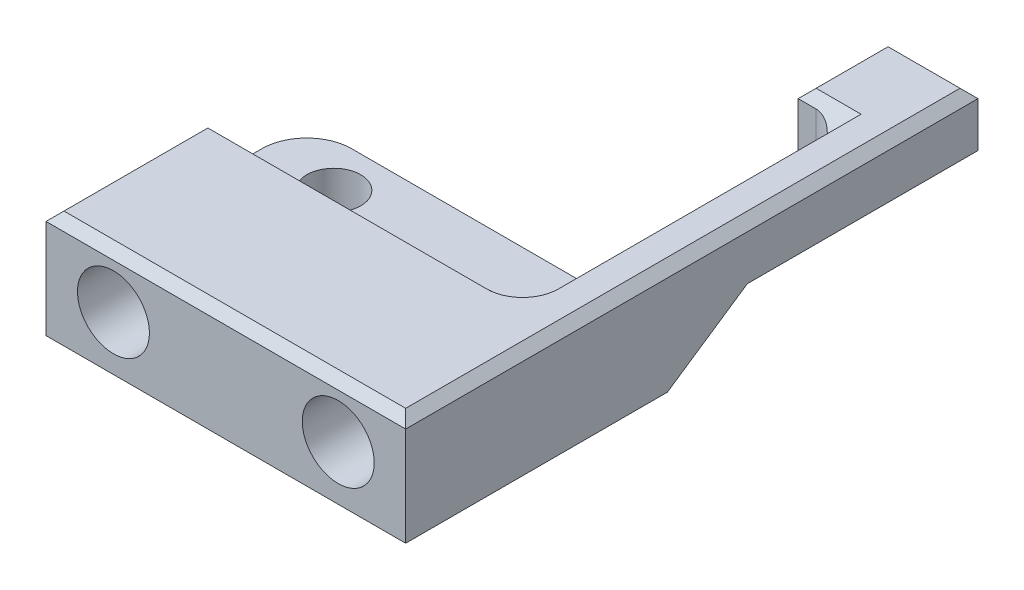
SolidWorks part; units mm, degrees
ref_plane "Front Plane" through (0, 0, 0) normal (0, 0, 1) x (1, 0, 0)
ref_plane "Top Plane" through (0, 0, 0) normal (0, 1, 0) x (1, 0, 0)
ref_plane "Right Plane" through (0, 0, 0) normal (1, 0, 0) x (0, 0, -1)
sketch "Sketch1" plane through (0, 0, 0) normal (0, 1, 0) x (1, 0, 0)
  line L1 (-20, -15) -> (20, -15)
  line L2 (-20, -15) -> (-20, 15)
  line L3 (-20, 15) -> (20, 15)
  line L4 (20, -15) -> (20, 15)
  line L5 (-20, -15) -> (20, 15) construction
  line L6 (-20, 15) -> (20, -15) construction
  point P0 (0, 0)
  dimension "D1" = 40
  dimension "D2" = 30
extrude "Boss-Extrude1" add sketch "Sketch1" along normal blind 12
sketch "Sketch2" plane through (0, 12, 0) normal (0, 1, 0) x (1, 0, 0)
  line L0 (20, 15) -> (-20, 15) construction
  line L1 (-12.5, 3) -> (12.5, 3)
  line L2 (-12.5, 3) -> (-12.5, 15)
  line L3 (-12.5, 15) -> (12.5, 15)
  line L4 (12.5, 3) -> (12.5, 15)
  line L5 (-12.5, 3) -> (12.5, 15) construction
  line L6 (-12.5, 15) -> (12.5, 3) construction
  point P0 (0, 9)
  dimension "D1" = 25
  dimension "D2" = 12.5
  dimension "D3" = 12
extrude "Cut-Extrude1" cut sketch "Sketch2" against normal blind 12
sketch "Sketch3" plane through (20, 0, 0) normal (1, 0, 0) x (0, 0, -1)
  line L0 (15, 12) -> (15, 0) construction
  circle A0 centre (9, 6) radius 4
  dimension "D1" = 6
extrude "Cut-Extrude2" cut sketch "Sketch3" against normal blind 100
fillet "Fillet1" radius 5 4 edges at (-16.25, 0, -15) (-16.25, 12, -15) (16.25, 0, -15) (16.25, 12, -15)
sketch "Sketch4" plane through (0, 0, 15) normal (0, 0, 1) x (1, 0, 0)
  line L0 (-20, 12) -> (-20, 0) construction
  circle A0 centre (-12.5, 6) radius 4
  circle A1 centre (12.5, 6) radius 4
  dimension "D1" = 7.5
  dimension "D2" = 25
extrude "Cut-Extrude3" cut sketch "Sketch4" against normal blind 12.5
sketch "Sketch6" plane through (0, 12, 0) normal (0, 1, 0) x (1, 0, 0)
  line L0 (-20, 10) -> (-20, -15) construction
  line L1 (-20, 3) -> (24.3469, 3)
  line L2 (-20, 3) -> (-20, 32.1532)
  line L3 (-20, 32.1532) -> (24.3469, 32.1532)
  line L4 (24.3469, 3) -> (24.3469, 32.1532)
extrude "Cut-Extrude4" cut sketch "Sketch6" against normal blind 100
sketch "Sketch7" plane through (0, 0, -3) normal (0, 0, -1) x (-1, 0, 0)
  line L0 (-20, 0) -> (-20, 12) construction
  line L1 (-20, 0) -> (20, 0)
  line L2 (-20, 0) -> (-20, 6)
  line L3 (-20, 6) -> (20, 6)
  line L4 (20, 0) -> (20, 6)
  line L5 (20, 0) -> (-20, 0) construction
  line L6 (20, 0) -> (20, 12) construction
extrude "Boss-Extrude2" add sketch "Sketch7" along normal blind 20
sketch "Sketch8" plane through (0, 6, 0) normal (0, 1, 0) x (1, 0, 0)
  line L1 (20, 3) -> (15, 3)
  line L2 (20, 3) -> (20, 48.6493)
  line L3 (20, 48.6493) -> (15, 48.6493)
  line L4 (15, 3) -> (15, 48.6493)
  line L5 (15, 48.6493) -> (10, 48.6493)
  line L6 (15, 48.6493) -> (15, 38.6493)
  line L7 (15, 38.6493) -> (10, 38.6493)
  line L8 (10, 48.6493) -> (10, 38.6493)
  line M1 (-20, 3) -> (20, 3)
  line M2 (20, 3) -> (20, 23)
  line M3 (20, 23) -> (-20, 23)
  dimension "D1" = 5
  dimension "D2" = 5
  dimension "D3" = 10
extrude "Boss-Extrude3" add sketch "Sketch8" along normal up to surface (6 mm away) contours L4 L2 L3 M3 | L4 M1 M2 M3 | L5 L8 L7 L4 region at (17.5, 6, -13) region at (17.5, 6, -35.8247) region at (12.5, 6, -43.6493) up to face at (0, 12, 6)
sketch "Sketch9" plane through (0, 6, 0) normal (0, 1, 0) x (1, 0, 0)
  line L0 (-20, 3) -> (15, 3) construction
  line L1 (-20, 23) -> (-20, 3) construction
  line L2 (15, 3) -> (15, 23) construction
  line L3 (-20, 23) -> (15, 23)
  line L4 (-20, 23) -> (-20, 14)
  line L5 (-20, 14) -> (15, 14)
  line L6 (15, 23) -> (15, 14)
  circle A0 centre (-12, 9) radius 3
  dimension "D1" = 6
  dimension "D2" = 8
  dimension "D3" = 9
extrude "Cut-Extrude5" cut sketch "Sketch9" against normal blind 20
chamfer "Chamfer2" distance 6 angle 56 1 edges at (17.5, 0, -23) first distance on face at (17.5, 3, -23)
fillet "Fillet2" radius 5 2 edges at (-20, 3, -14) (15, 3, -14)
fillet "Fillet3" radius 3 3 edges at (15, 6, -11) (15, 9, -3)
chamfer "Chamfer3" distance 1 angle 45 9 edges at (0, 12, 15) (-20, 12, 6) (-4, 12, -3) (14.1213, 12, -3.8787) (15, 12, -22.3247) (12.5, 12, -38.6493) (10, 12, -43.6493) (15, 12, -48.6493) (20, 12, -16.8247)
fillet "Fillet4" radius 3 1 edges at (15, 8.5, -38.6493)
